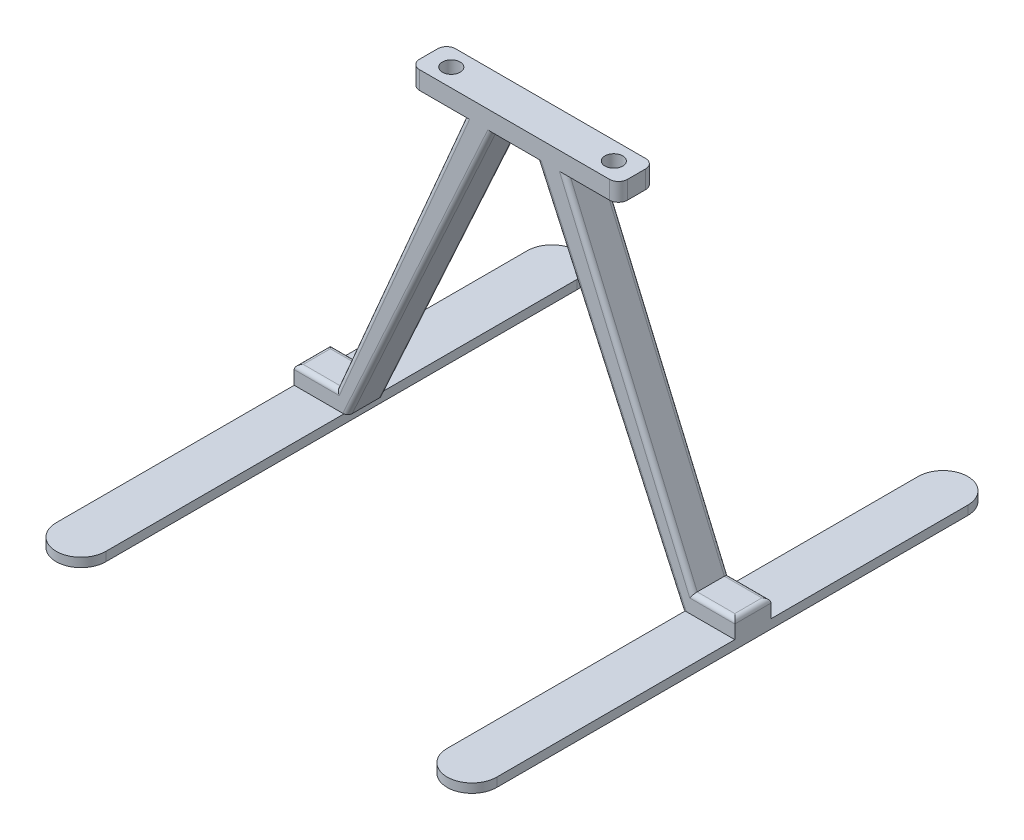
SolidWorks part; units mm, degrees
ref_plane "Front Plane" through (0, 0, 0) normal (0, 0, 1) x (1, 0, 0)
ref_plane "Top Plane" through (0, 0, 0) normal (0, 1, 0) x (1, 0, 0)
ref_plane "Right Plane" through (0, 0, 0) normal (1, 0, 0) x (0, 0, -1)
sketch "Sketch1" plane through (0, 0, 0) normal (0, 1, 0) x (1, 0, 0)
  line L0 (0, 0) -> (-22.86, 0) construction
  line L1 (0, 0) -> (0, 17.5181) construction
  line L2 (26.7058, 5.08) -> (-26.7058, 5.08)
  line L3 (-29.2458, 2.54) -> (-29.2458, -2.54)
  line L4 (-26.7058, -5.08) -> (26.7058, -5.08)
  line L5 (29.2458, 2.54) -> (29.2458, -2.54)
  circle A0 centre (-22.86, 0) radius 2.5
  circle A1 centre (22.86, 0) radius 2.5
  arc A2 (26.7058, 5.08) -> (29.2458, 2.54) centre (26.7058, 2.54) cw
  arc A3 (29.2458, -2.54) -> (26.7058, -5.08) centre (26.7058, -2.54) cw
  arc A4 (-29.2458, -2.54) -> (-26.7058, -5.08) centre (-26.7058, -2.54) ccw
  arc A5 (-29.2458, 2.54) -> (-26.7058, 5.08) centre (-26.7058, 2.54) cw
  point P12 (0, -5.08)
  point P13 (0, 5.08)
  point P15 (29.2458, 5.08)
  point P18 (29.2458, -5.08)
  point P21 (-29.2458, -5.08)
  point P24 (-29.2458, 5.08)
  dimension "D2" = 5
  dimension "D3" = 5.08
  dimension "D5" = 2.54
  dimension "D1" = 22.86
  dimension "D4" = 5.08
extrude "Boss-Extrude1" add sketch "Sketch1" along normal blind 5.08
sketch "Sketch2" plane through (0, 0, 5.08) normal (0, 0, 1) x (1, 0, 0)
  line L0 (-14.0071, 0) -> (-50.125, -84.328)
  line L1 (-26.7058, 0) -> (26.7058, 0) construction
  line L2 (-14.0071, 0) -> (-6.1223, 0)
  line L3 (-6.1223, 0) -> (-46.8928, -89.408)
  line L4 (0, 0) -> (0, -89.408) construction
  line L5 (0, -89.408) -> (-50.8, -89.408) construction
  line L6 (50.8, -89.408) -> (61.9471, -89.408)
  line L7 (-50.8, -89.408) -> (-61.9471, -89.408)
  line L9 (-50.125, -84.328) -> (-61.9471, -84.328)
  line L10 (-61.9471, -89.408) -> (-61.9471, -84.328)
  line L11 (61.9471, -89.408) -> (61.9471, -84.328)
  line L12 (50.125, -84.328) -> (61.9471, -84.328)
  line L13 (14.0071, 0) -> (50.125, -84.328)
  line L14 (14.0071, 0) -> (6.1223, 0)
  line L15 (6.1223, 0) -> (46.8928, -89.408)
  line L17 (-46.8928, -89.408) -> (-50.8, -89.408)
  line L18 (46.8928, -89.408) -> (50.8, -89.408)
  dimension "D1" = 89.408
  dimension "D2" = 50.8
  dimension "D3" = 5.08
extrude "Boss-Extrude2" add sketch "Sketch2" against normal blind 10.16
fillet "Fillet2" radius 1.27 6 edges at (56.036, -84.328, -5.08) (61.9471, -84.328, 0) (56.036, -84.328, 5.08) (-56.036, -84.328, -5.08) (-61.9471, -84.328, 0) (-56.036, -84.328, 5.08)
fillet "Fillet3" radius 1.27 8 edges at (32.338, -42.799, 5.08) (26.5076, -44.704, 5.08) (32.338, -42.799, -5.08) (26.5076, -44.704, -5.08) (-26.5076, -44.704, -5.08) (-32.338, -42.799, -5.08) (-32.338, -42.799, 5.08) (-26.5076, -44.704, 5.08)
sketch "Sketch3" plane through (0, -89.408, 0) normal (0, -1, 0) x (1, 0, 0)
  line L0 (0, 0) -> (0, 54.3232) construction
  line L1 (47.9875, 72.0059) -> (47.9875, -60.441)
  line L2 (61.9471, 72.0059) -> (61.9471, -60.441)
  line L3 (-61.9471, 72.0059) -> (-61.9471, -60.441)
  line L4 (-47.9875, 72.0059) -> (-47.9875, -60.441)
  arc A0 (-61.9471, 72.0059) -> (-47.9875, 72.0059) centre (-54.9673, 72.0059) cw
  arc A1 (-47.9875, -60.441) -> (-61.9471, -60.441) centre (-54.9673, -60.441) cw
  arc A2 (47.9875, -60.441) -> (61.9471, -60.441) centre (54.9673, -60.441) ccw
  arc A3 (61.9471, 72.0059) -> (47.9875, 72.0059) centre (54.9673, 72.0059) ccw
extrude "Boss-Extrude3" add sketch "Sketch3" along normal blind 2.54
